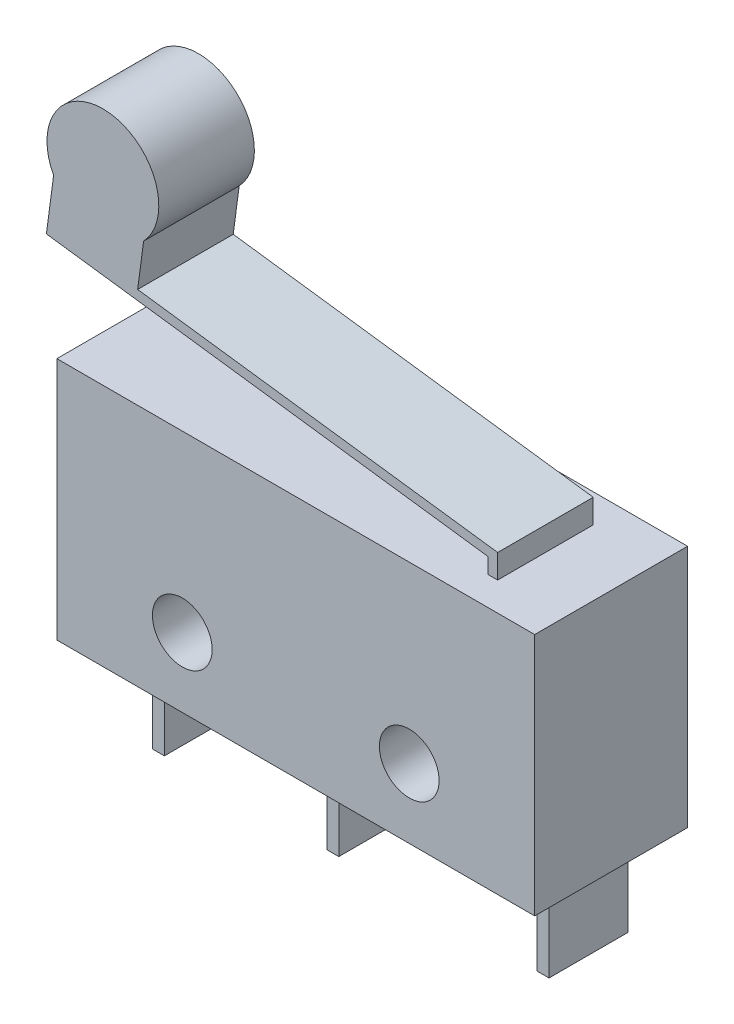
SolidWorks part; units mm, degrees
ref_plane "Frontal Plane" through (0, 0, 0) normal (0, 0, 1) x (1, 0, 0)
ref_plane "Horizontal Plane" through (0, 0, 0) normal (0, 1, 0) x (1, 0, 0)
ref_plane "Profile Plane" through (0, 0, 0) normal (1, 0, 0) x (0, 0, -1)
sketch "Sketch1" plane through (0, 0, 0) normal (0, 0, 1) x (1, 0, 0)
  line L1 (-10, -5.1) -> (10, -5.1)
  line L2 (-10, -5.1) -> (-10, 5.1)
  line L3 (-10, 5.1) -> (10, 5.1)
  line L4 (10, -5.1) -> (10, 5.1)
  line L5 (-10, -5.1) -> (10, 5.1) construction
  line L6 (-10, 5.1) -> (10, -5.1) construction
  circle A0 centre (-4.75, -2.2) radius 1.25
  circle A1 centre (4.75, -2.2) radius 1.25
  point P0 (0, 0)
  dimension "D3" = 2.5
  dimension "D1" = 20
  dimension "D2" = 10.2
  dimension "D4" = 2.9
  dimension "D5" = 9.5
  dimension "D6" = 5.25
extrude "Boss-Extrude1" add sketch "Sketch1" along normal mid plane 6.4
sketch "Sketch2" plane through (0, 0, 0) normal (0, 0, 1) x (1, 0, 0)
  line L0 (7.25, 5.1) -> (6.85, 5.1)
  line L1 (10, 5.1) -> (-10, 5.1) construction
  line L2 (6.85, 5.1) -> (6.85, 5.7496)
  line L3 (6.85, 5.7496) -> (-11.6376, 8.2019)
  line L6 (-7.818, 8.0988) -> (7.25, 6.1)
  line L7 (7.25, 6.1) -> (7.25, 5.1)
  line L10 (-11.1563, 11.8302) -> (-7.3893, 11.3305) construction
  line L11 (10, -5.1) -> (10, 5.1) construction
  line L12 (-11.3359, 10.4762) -> (-11.6376, 8.2019)
  line L13 (-11.1563, 11.8302) -> (-11.3359, 10.4762) construction
  line L14 (-7.5689, 9.9765) -> (-7.818, 8.0988)
  line L15 (-7.5689, 9.9765) -> (-7.3893, 11.3305) construction
  line L16 (-10, -5.1) -> (10, -5.1) construction
  arc A2 (-7.5689, 9.9765) -> (-11.3359, 10.4762) centre (-9.2728, 11.5803) ccw
  point P9 (-8.9651, 13.9)
  dimension "D3" = 4.68
  dimension "D1" = 0.4
  dimension "D2" = 0.4
  dimension "D5" = 1
  dimension "D7" = 3.66
  dimension "D9" = 2.75
  dimension "D4" = 3.8
  dimension "D6" = 19
  dimension "D8" = 19
extrude "Boss-Extrude2" add sketch "Sketch2" along normal mid plane 4
sketch "Sketch3" plane through (0, 0, 0) normal (1, 0, 0) x (0, 0, -1)
  line L0 (-1.65, -5.1) -> (-1.65, -8.6)
  line L1 (-3.2, -5.1) -> (3.2, -5.1) construction
  line L2 (-1.65, -8.6) -> (1.65, -8.6)
  line L3 (1.65, -8.6) -> (1.65, -5.1)
  line L4 (1.65, -5.1) -> (-1.65, -5.1)
  point P4 (0, -8.6)
  dimension "D1" = 3.5
  dimension "D2" = 3.3
extrude "Boss-Extrude3" add sketch "Sketch3" along normal mid plane 0.5
extrude "Boss-Extrude4" add sketch "Sketch3<2>" against normal mid plane 0.5 from offset 8.8
sketch "Sketch3<2>" plane through (0, 0, 0) normal (1, 0, 0) x (0, 0, -1) same geometry as "Sketch3"
extrude "Boss-Extrude5" add sketch "Sketch3<3>" along normal mid plane 0.5 from offset 7.3 offset against normal yes
sketch "Sketch3<3>" plane through (0, 0, 0) normal (1, 0, 0) x (0, 0, -1) same geometry as "Sketch3"
equation "\"D7@Sketch2\"=6-(\"D3@Sketch2\"*.5)"
